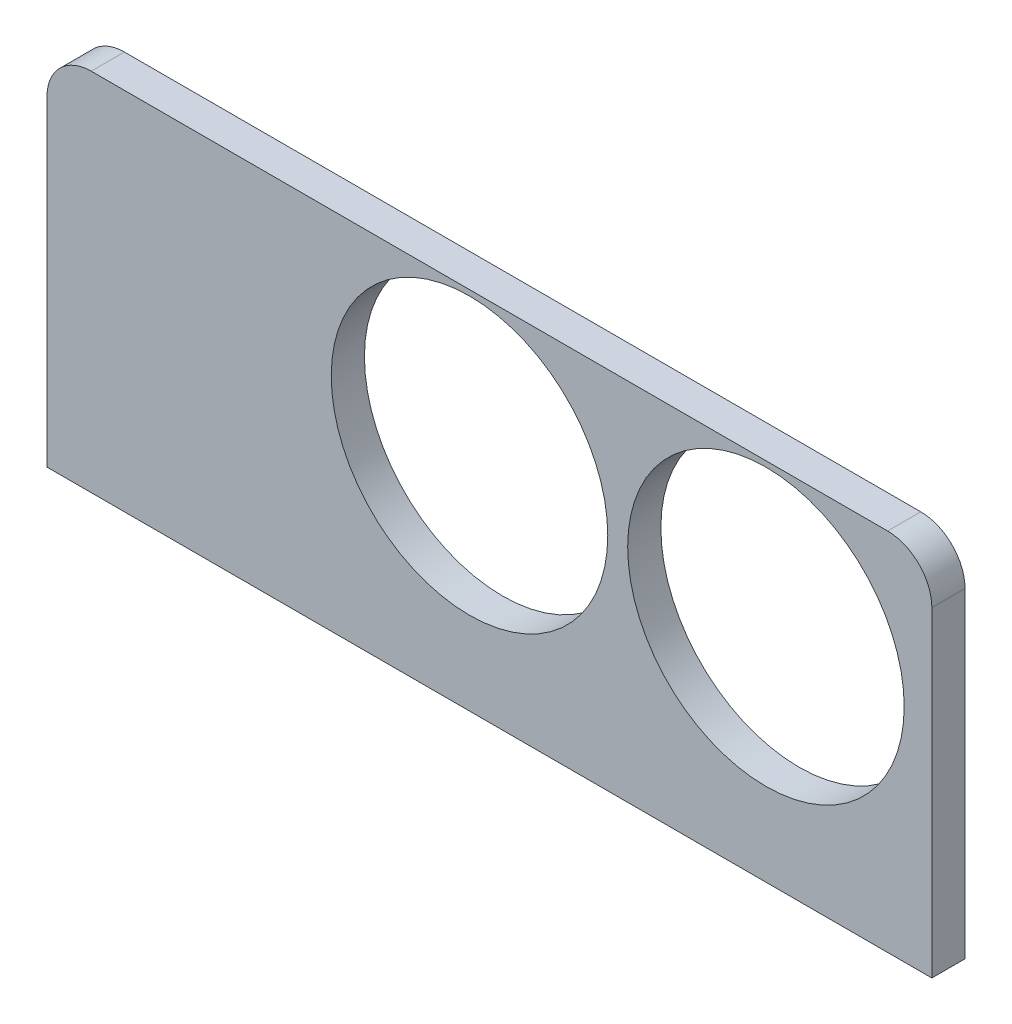
SolidWorks part; units mm, degrees
ref_plane "Front Plane" through (0, 0, 0) normal (0, 0, 1) x (1, 0, 0)
ref_plane "Top Plane" through (0, 0, 0) normal (0, 1, 0) x (1, 0, 0)
ref_plane "Right Plane" through (0, 0, 0) normal (1, 0, 0) x (0, 0, -1)
sketch "Sketch1" plane through (0, 0, 0) normal (0, 0, 1) x (1, 0, 0)
  line L1 (-20, -8.25) -> (20, -8.25)
  line L2 (-20, -8.25) -> (-20, 8.25)
  line L3 (-20, 8.25) -> (20, 8.25)
  line L4 (20, -8.25) -> (20, 8.25)
  line L5 (-20, -8.25) -> (20, 8.25) construction
  line L6 (-20, 8.25) -> (20, -8.25) construction
  line L7 (-20, 1.75) -> (20, 1.75) construction
  circle A0 centre (-0.9, 1.75) radius 6.25
  circle A1 centre (12.5, 1.75) radius 6.25
  point P4 (0, 0)
  point P5 (-6.4265, 1.75)
  point P6 (-1.6729, 1.75)
  dimension "D1" = 12.5
  dimension "D2" = 13.4
  dimension "D3" = 6.5
  dimension "D6" = 7.5
  dimension "D4" = 40
  dimension "D5" = 16.5
extrude "Boss-Extrude1" add sketch "Sketch1" along normal blind 1.5
fillet "Fillet1" radius 2 2 edges at (20, 8.25, 0.75) (-20, 8.25, 0.75)
